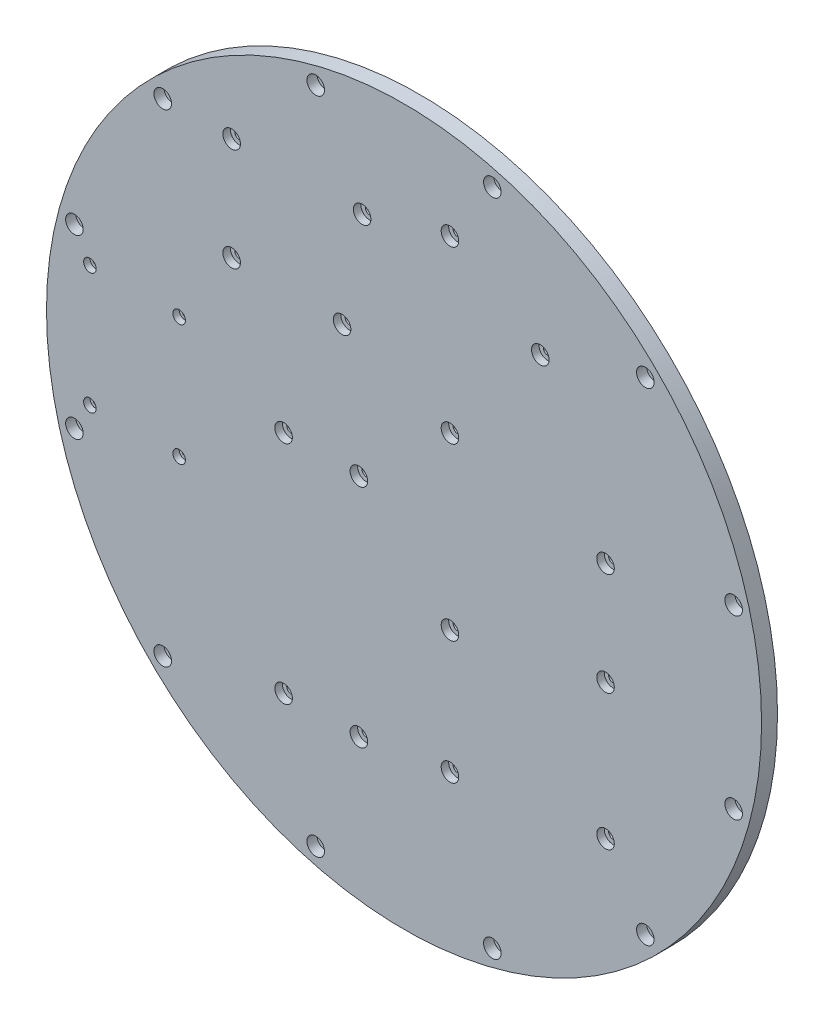
SolidWorks part; units mm, degrees
ref_plane "Plan de face" through (0, 0, 0) normal (0, 0, 1) x (1, 0, 0)
ref_plane "Plan de dessus" through (0, 0, 0) normal (0, 1, 0) x (1, 0, 0)
ref_plane "Plan de droite" through (0, 0, 0) normal (1, 0, 0) x (0, 0, -1)
sketch "Esquisse1" plane through (0, 0, 0) normal (0, 0, 1) x (1, 0, 0)
  line L0 (0, 0) -> (0, 136) construction
  line L1 (0, 0) -> (-35.1994, 131.3659) construction
  circle A3 centre (0, 0) radius 136 construction
  circle A14 centre (-35.1994, 131.3659) radius 1.75
  circle A41 centre (0, 0) radius 142.5
  circle A42 centre (35.1994, 131.3659) radius 1.75
  circle A43 centre (96.1665, 96.1665) radius 1.75
  circle A44 centre (131.3659, 35.1994) radius 1.75
  circle A45 centre (131.3659, -35.1994) radius 1.75
  circle A46 centre (96.1665, -96.1665) radius 1.75
  circle A47 centre (35.1994, -131.3659) radius 1.75
  circle A48 centre (-35.1994, -131.3659) radius 1.75
  circle A49 centre (-96.1665, -96.1665) radius 1.75
  circle A50 centre (-131.3659, -35.1994) radius 1.75
  circle A51 centre (-131.3659, 35.1994) radius 1.75
  circle A52 centre (-96.1665, 96.1665) radius 1.75
  point P31 (0, 0)
  point P34 (0, 0)
  point P41 (0, 0)
  dimension "D1" = 272
  dimension "D3" = 3.5
  dimension "D4" = 285
  dimension "D2" = 15
extrude "Boss.-Extru.1" add sketch "Esquisse1" along normal blind 6.35
sketch "Esquisse2" plane through (0, 0, 6.35) normal (0, 0, 1) x (1, 0, 0)
  circle A12 centre (35.1994, 131.3659) radius 3.5
  circle A13 centre (96.1665, 96.1665) radius 3.5
  circle A14 centre (131.3659, 35.1994) radius 3.5
  circle A15 centre (131.3659, -35.1994) radius 3.5
  circle A16 centre (96.1665, -96.1665) radius 3.5
  circle A17 centre (35.1994, -131.3659) radius 3.5
  circle A18 centre (-35.1994, -131.3659) radius 3.5
  circle A19 centre (-96.1665, -96.1665) radius 3.5
  circle A20 centre (-131.3659, -35.1994) radius 3.5
  circle A21 centre (-131.3659, 35.1994) radius 3.5
  circle A22 centre (-96.1665, 96.1665) radius 3.5
  circle A23 centre (-35.1994, 131.3659) radius 3.5
  point P20 (0, 0)
  point P27 (0, 0)
  dimension "D1" = 7
extrude "Enlèv. mat.-Extru.1" cut sketch "Esquisse2" against normal blind 4
sketch "Esquisse3" plane through (0, 0, 6.35) normal (0, 0, 1) x (1, 0, 0)
  line L0 (-125.1958, -24.13) -> (-125.1958, 24.13) construction
  line L1 (-125.1958, 24.13) -> (-89.6358, 24.13) construction
  line L2 (-89.6358, 24.13) -> (-89.6358, -24.13) construction
  line L3 (-89.6358, -24.13) -> (-125.1958, -24.13) construction
  circle A0 centre (0, 0) radius 127.5 construction
  circle A3 centre (-125.1958, -24.13) radius 1.25
  circle A4 centre (-125.1958, 24.13) radius 1.25
  circle A5 centre (-89.6358, 24.13) radius 1.25
  circle A6 centre (-89.6358, -24.13) radius 1.25
  dimension "D1" = 255
  dimension "D2" = 35.56
  dimension "D4" = 2.5
  dimension "D3" = 48.26
extrude "Enlèv. mat.-Extru.2" cut sketch "Esquisse3" against normal up to next
sketch "Esquisse4" plane through (0, 0, 6.35) normal (0, 0, 1) x (1, 0, 0)
  circle A0 centre (-125.1958, -24.13) radius 2.5
  circle A1 centre (-125.1958, 24.13) radius 2.5
  circle A2 centre (-89.6358, 24.13) radius 2.5
  circle A3 centre (-89.6358, -24.13) radius 2.5
  dimension "D1" = 5
extrude "Enlèv. mat.-Extru.3" cut sketch "Esquisse4" against normal blind 2.5
sketch "Esquisse5" plane through (0, 0, 6.35) normal (0, 0, 1) x (1, 0, 0)
  circle A0 centre (-48, -85) radius 1.75
  circle A1 centre (-48, 5) radius 1.75
  circle A2 centre (-18, 5) radius 1.75
  circle A3 centre (-18, -85) radius 1.75
  circle A4 centre (0, 0) radius 142.5 construction
  circle A5 centre (0, 0) radius 142.5 construction
  dimension "D4" = 3.5
  dimension "D1" = 90
  dimension "D2" = 30
  dimension "D3" = 5
  dimension "D5" = 18
extrude "Enlèv. mat.-Extru.4" cut sketch "Esquisse5" against normal up to next
sketch "Esquisse6" plane through (0, 0, 6.35) normal (0, 0, 1) x (1, 0, 0)
  circle A0 centre (-48, -85) radius 3.5
  circle A1 centre (-18, -85) radius 3.5
  circle A2 centre (-48, 5) radius 3.5
  circle A3 centre (-18, 5) radius 3.5
  dimension "D1" = 7
extrude "Enlèv. mat.-Extru.5" cut sketch "Esquisse6" against normal blind 3
sketch "Esquisse7" plane through (0, 0, 6.35) normal (0, 0, 1) x (1, 0, 0)
  circle A0 centre (-68.7, 55) radius 1.75
  circle A1 centre (-68.7, 96) radius 1.75
  circle A2 centre (-24.7, 54) radius 1.75
  circle A3 centre (-16.7, 96) radius 1.75
  circle A5 centre (-18, 5) radius 3.5 construction
  circle A7 centre (-48, 5) radius 3.5 construction
  circle A8 centre (-18, 5) radius 3.5 construction
  circle A9 centre (-48, 5) radius 3.5 construction
  dimension "D5" = 3.5
  dimension "D7" = 50
  dimension "D1" = 44
  dimension "D2" = 41
  dimension "D3" = 42
  dimension "D4" = 52
  dimension "D6" = 6.7
extrude "Enlèv. mat.-Extru.6" cut sketch "Esquisse7" against normal up to next
sketch "Esquisse8" plane through (0, 0, 6.35) normal (0, 0, 1) x (1, 0, 0)
  circle A0 centre (-68.7, 55) radius 3.5
  circle A1 centre (-68.7, 96) radius 3.5
  circle A2 centre (-24.7, 54) radius 3.5
  circle A3 centre (-16.7, 96) radius 3.5
  dimension "D1" = 7
extrude "Enlèv. mat.-Extru.7" cut sketch "Esquisse8" against normal blind 3
sketch "Esquisse9" plane through (0, 0, 6.35) normal (0, 0, -1) x (-1, 0, 0)
  circle A0 centre (-18.3, 106) radius 1.75
  circle A1 centre (-18.3, 38) radius 1.75
  circle A2 centre (-54.3, 83) radius 1.75
  circle A3 centre (-80.3, 24) radius 1.75
  circle A6 centre (16.7, 96) radius 1.75 construction
  circle A7 centre (16.7, 96) radius 1.75 construction
  dimension "D1" = 3.5
  dimension "D2" = 68
  dimension "D3" = 23
  dimension "D4" = 36
  dimension "D5" = 62
  dimension "D6" = 35
  dimension "D7" = 82
  dimension "D8" = 10
extrude "Enlèv. mat.-Extru.8" cut sketch "Esquisse9" along normal up to next
sketch "Esquisse10" plane through (0, 0, 6.35) normal (0, 0, 1) x (1, 0, 0)
  circle A0 centre (18.3, 38) radius 3.5
  circle A1 centre (18.3, 106) radius 3.5
  circle A2 centre (54.3, 83) radius 3.5
  circle A3 centre (80.3, 24) radius 3.5
  dimension "D1" = 7
extrude "Enlèv. mat.-Extru.9" cut sketch "Esquisse10" against normal blind 3
sketch "Esquisse11" plane through (0, 0, 6.35) normal (0, 0, -1) x (-1, 0, 0)
  circle A0 centre (-18.3, -30) radius 1.75
  circle A1 centre (-18.3, -79) radius 1.75
  circle A2 centre (-80.3, -17) radius 1.75
  circle A3 centre (-80.3, -71) radius 1.75
  circle A7 centre (-18.3, 38) radius 1.75 construction
  circle A8 centre (-18.3, 38) radius 1.75 construction
  dimension "D1" = 3.5
  dimension "D2" = 49
  dimension "D6" = 55
  dimension "D3" = 62
  dimension "D4" = 13
  dimension "D5" = 54
extrude "Enlèv. mat.-Extru.10" cut sketch "Esquisse11" along normal up to next
sketch "Esquisse12" plane through (0, 0, 6.35) normal (0, 0, 1) x (1, 0, 0)
  circle A0 centre (18.3, -79) radius 3.5
  circle A1 centre (18.3, -30) radius 3.5
  circle A2 centre (80.3, -17) radius 3.5
  circle A3 centre (80.3, -71) radius 3.5
  dimension "D1" = 7
extrude "Enlèv. mat.-Extru.11" cut sketch "Esquisse12" against normal blind 3
